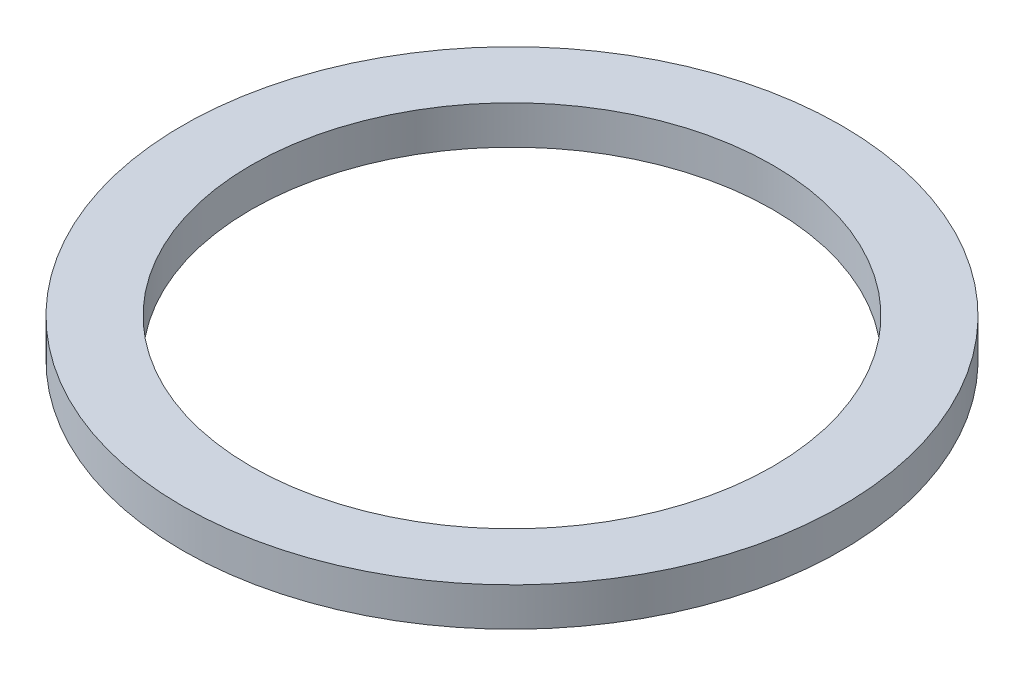
SolidWorks part; units mm, degrees
ref_plane "Front Plane" through (0, 0, 0) normal (0, 0, 1) x (1, 0, 0)
ref_plane "Top Plane" through (0, 0, 0) normal (0, 1, 0) x (1, 0, 0)
ref_plane "Right Plane" through (0, 0, 0) normal (1, 0, 0) x (0, 0, -1)
sketch "Sketch1" plane through (0, 0, 0) normal (0, 1, 0) x (1, 0, 0)
  circle A0 centre (0, 0) radius 60
  dimension "FLANGE_OD" = 120
extrude "Boss-Extrude1" add sketch "Sketch1" along normal blind 7
sketch "Sketch2" plane through (0, 0, 0) normal (0, 1, 0) x (1, 0, 0)
  circle A0 centre (0, 0) radius 47.5
  dimension "BORE_D" = 95
extrude "Cut-Extrude1" cut sketch "Sketch2" along normal through all
sketch "Sketch3" plane through (0, 7, 0) normal (0, 1, 0) x (1, 0, 0)
  circle A0 centre (0, 0) radius 25.9919 construction
  circle A1 centre (-25.9919, 0) radius 1.5078
  dimension "BOLT_D" = 3.0156
  dimension "BOLT_PCD" = 51.9839
extrude "Cut-Extrude2" cut sketch "Sketch3" against normal blind 6.0325 rebuild error yes
pattern_circular "CirPattern1" count 6 over 360 rebuild error yes
